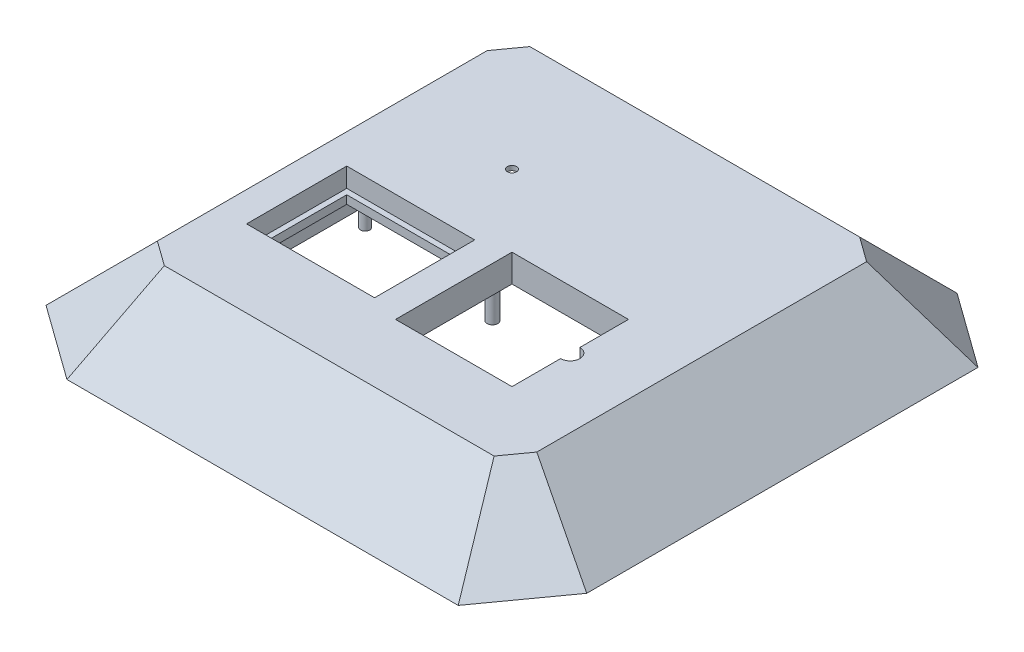
SolidWorks part; units mm, degrees
ref_plane "Front Plane" through (0, 0, 0) normal (0, 0, 1) x (1, 0, 0)
ref_plane "Top Plane" through (0, 0, 0) normal (0, 1, 0) x (1, 0, 0)
ref_plane "Right Plane" through (0, 0, 0) normal (1, 0, 0) x (0, 0, -1)
sketch "Sketch1" plane through (0, 0, 0) normal (0, 1, 0) x (1, 0, 0)
  line L0 (-47.3454, -21.7516) -> (37.6546, -21.7516)
  line L1 (37.6546, -21.7516) -> (49.3368, -5.5181)
  line L2 (49.3368, -5.5181) -> (49.3368, 79.4819)
  line L3 (49.3368, 79.4819) -> (33.1033, 91.1641)
  line L4 (33.1033, 91.1641) -> (-51.8967, 91.1641)
  line L5 (-51.8967, 91.1641) -> (-63.5789, 74.9306)
  line L6 (-63.5789, 74.9306) -> (-63.5789, -10.0694)
  line L7 (-63.5789, -10.0694) -> (-47.3454, -21.7516)
  dimension "D2" = 85
  dimension "D3" = 85
  dimension "D4" = 144.26
  dimension "D5" = 144.26
  dimension "D6" = 85
  dimension "D7" = 144.26
  dimension "D8" = 20
  dimension "D9" = 85
  dimension "D10" = 20
  dimension "D11" = 20
extrude "Boss-Extrude2" add sketch "Sketch1" along normal blind 16
sketch "Sketch4" plane through (0, 0, 0) normal (0, -1, 0) x (1, 0, 0)
  line L16 (-42.1868, 5.7516) -> (-47.5789, 1.8712)
  line L17 (-47.5789, 1.8712) -> (-47.5789, -69.772)
  line L18 (-47.5789, -69.772) -> (-43.6985, -75.1641)
  line L19 (-43.6985, -75.1641) -> (27.9447, -75.1641)
  line L20 (27.9447, -75.1641) -> (33.3368, -71.2838)
  line L21 (33.3368, -71.2838) -> (33.3368, 0.3594)
  line L22 (33.3368, 0.3594) -> (29.4564, 5.7516)
  line L23 (29.4564, 5.7516) -> (-42.1868, 5.7516)
  line L24 (-42.1868, 5.7516) -> (-47.5789, 1.8712)
  line L25 (-47.5789, 1.8712) -> (-47.5789, -69.772)
  line L26 (-47.5789, -69.772) -> (-43.6985, -75.1641)
  line L27 (-43.6985, -75.1641) -> (27.9447, -75.1641)
  line L28 (27.9447, -75.1641) -> (33.3368, -71.2838)
  line L29 (33.3368, -71.2838) -> (33.3368, 0.3594)
  line L30 (33.3368, 0.3594) -> (29.4564, 5.7516)
  line L31 (29.4564, 5.7516) -> (-42.1868, 5.7516)
  dimension "D1" = 16
chamfer "Chamfer1" distance 16 angle 45 8 edges at (-63.5789, 16, -32.4306) (-57.7378, 16, -83.0473) (-9.3967, 16, -91.1641) (41.22, 16, -85.323) (49.3368, 16, -36.9819) (43.4957, 16, 13.6348) (-4.8454, 16, 21.7516) (-55.4621, 16, 15.9105)
extrude "Cut-Extrude3" cut sketch "Sketch4" against normal blind 10
sketch "Sketch6" plane through (0, 16, 0) normal (0, 1, 0) x (1, 0, 0)
  line L0 (33.3368, -0.3594) -> (33.3368, 71.2838) construction
  line L1 (-6.9632, 34.5484) -> (18.3368, 34.5484)
  line L2 (-6.9632, 34.5484) -> (-6.9632, 9.2484)
  line L3 (-6.9632, 9.2484) -> (18.3368, 9.2484)
  line L4 (18.3368, 34.5484) -> (18.3368, 9.2484)
  line L5 (-42.1868, -5.7516) -> (29.4564, -5.7516) construction
  dimension "D1" = 25.3
  dimension "D2" = 25.3
  dimension "D3" = 15
  dimension "D4" = 15
extrude "Cut-Extrude4" cut sketch "Sketch6" against normal up to next
sketch "Sketch7" plane through (0, 10, 0) normal (0, -1, 0) x (1, 0, 0)
  line L0 (18.3368, -9.2484) -> (18.3368, -34.5484) construction
  circle A0 centre (18.3368, -21.8984) radius 2.0981
extrude "Cut-Extrude5" cut sketch "Sketch7" against normal up to next
sketch "Sketch8" plane through (0, 10, 0) normal (0, -1, 0) x (1, 0, 0)
  line L0 (-11.7632, -21.9984) -> (30.1662, -21.9984) construction
  line L1 (-11.7632, -8.8984) -> (24.2368, -8.8984)
  line L2 (-11.7632, -8.8984) -> (-11.7632, -35.0984)
  line L3 (-11.7632, -35.0984) -> (24.2368, -35.0984)
  line L4 (24.2368, -8.8984) -> (24.2368, -35.0984)
  line L5 (6.2368, -8.8984) -> (6.2368, -38.2867) construction
  line L6 (33.3368, -71.2838) -> (33.3368, 0.3594) construction
  line L7 (29.4564, 5.7516) -> (-42.1868, 5.7516) construction
  circle A0 centre (-9.2132, -11.4484) radius 1.15
  circle A1 centre (21.6868, -11.4484) radius 1.15
  circle A2 centre (21.6868, -32.5484) radius 1.15
  circle A3 centre (-9.2132, -32.5484) radius 1.15
  dimension "D3" = 2.3
  dimension "D4" = 2.55
  dimension "D5" = 2.55
  dimension "D6" = 9.1
  dimension "D1" = 36
  dimension "D2" = 26.2
  dimension "D7" = 14.65
extrude "Boss-Extrude3" add sketch "Sketch8" along normal blind 7 contours A0 | A1 | A2 | A3 region at (-9.2132, 10, -11.4484) region at (21.6868, 10, -11.4484) region at (21.6868, 10, -32.5484)
sketch "Sketch9" plane through (0, 10, 0) normal (0, -1, 0) x (1, 0, 0)
  line L2 (-47.5789, 1.8712) -> (-47.5789, -69.772) construction
  line L3 (-43.6985, -75.1641) -> (27.9447, -75.1641) construction
  circle A0 centre (-22.5789, -50.1641) radius 15.65
  dimension "D1" = 25
  dimension "D2" = 25
  dimension "D3" = 31.3
extrude "Cut-Extrude6" cut sketch "Sketch9" against normal blind 5
sketch "Sketch10" plane through (0, 15, 0) normal (0, -1, 0) x (1, 0, 0)
  circle A0 centre (-22.5789, -50.1641) radius 1
  dimension "D1" = 2
extrude "Cut-Extrude7" cut sketch "Sketch10" against normal up to next
sketch "Sketch11" plane through (0, 16, 0) normal (0, 1, 0) x (1, 0, 0)
  line L0 (-14.7144, 21.8984) -> (-6.9632, 21.8984) construction
  line L1 (-14.7144, 35.3984) -> (-39.7144, 35.3984)
  line L2 (-14.7144, 35.3984) -> (-14.7144, 8.3984)
  line L3 (-14.7144, 8.3984) -> (-39.7144, 8.3984)
  line L4 (-39.7144, 35.3984) -> (-39.7144, 8.3984)
  line L5 (-6.9632, 34.5484) -> (-6.9632, 9.2484) construction
  line L6 (-27.2144, 35.3984) -> (-27.2144, 2.0931) construction
  line L7 (-14.7144, 21.8984) -> (-44.3409, 21.8984) construction
  circle A0 centre (-37.5644, 33.2484) radius 1
  circle A1 centre (-16.8644, 33.2484) radius 1
  circle A2 centre (-16.8644, 10.5484) radius 1
  circle A3 centre (-37.5644, 10.5484) radius 1
  dimension "D3" = 2
  dimension "D4" = 2.15
  dimension "D5" = 2.15
  dimension "D1" = 25
  dimension "D2" = 27
extrude "Boss-Extrude4" add sketch "Sketch11" against normal blind 10 contours A0 | A1 | A2 | A3
sketch "Sketch12" plane through (0, 16, 0) normal (0, 1, 0) x (1, 0, 0)
  line L0 (-14.7144, 35.3984) -> (-14.7144, 8.3984) construction
  line L1 (-39.9144, 31.5984) -> (-14.5144, 31.5984)
  line L2 (-39.9144, 31.5984) -> (-39.9144, 12.2384)
  line L3 (-39.9144, 12.2384) -> (-14.5144, 12.2384)
  line L4 (-14.5144, 31.5984) -> (-14.5144, 12.2384)
  line L5 (-39.7144, 35.3984) -> (-39.7144, 8.3984) construction
  line L6 (-14.7144, 35.3984) -> (-39.7144, 35.3984) construction
  line L7 (-14.7144, 8.3984) -> (-39.7144, 8.3984) construction
  dimension "D1" = 0.2
  dimension "D2" = 0.2
  dimension "D3" = 3.8
  dimension "D4" = 3.84
extrude "Cut-Extrude8" cut sketch "Sketch12" against normal through all
sketch "Sketch13" plane through (0, 16, 0) normal (0, 1, 0) x (1, 0, 0)
  line L0 (-14.5144, 31.5984) -> (-39.9144, 31.5984) construction
  line L1 (-41.1144, 32.7984) -> (-13.3144, 32.7984)
  line L2 (-41.1144, 32.7984) -> (-41.1144, 11.0384)
  line L3 (-41.1144, 11.0384) -> (-13.3144, 11.0384)
  line L4 (-13.3144, 32.7984) -> (-13.3144, 11.0384)
  line L5 (-39.9144, 31.5984) -> (-39.9144, 12.2384) construction
  line L6 (-14.5144, 12.2384) -> (-14.5144, 31.5984) construction
  line L7 (-39.9144, 12.2384) -> (-14.5144, 12.2384) construction
  dimension "D1" = 1.2
  dimension "D2" = 1.2
  dimension "D3" = 1.2
  dimension "D4" = 1.2
extrude "Cut-Extrude9" cut sketch "Sketch13" against normal blind 4.2
